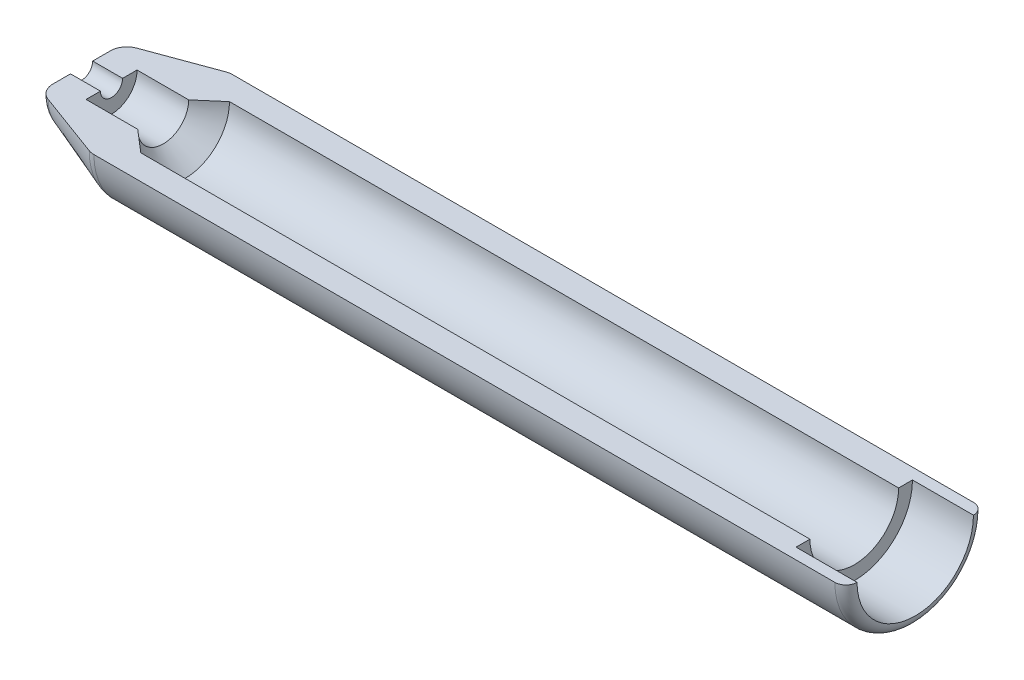
SolidWorks part; units mm, degrees
ref_plane "Front Plane" through (0, 0, 0) normal (0, 0, 1) x (1, 0, 0)
ref_plane "Top Plane" through (0, 0, 0) normal (0, 1, 0) x (1, 0, 0)
ref_plane "Right Plane" through (0, 0, 0) normal (1, 0, 0) x (0, 0, -1)
sketch "Sketch1" plane through (0, 0, 0) normal (0, 1, 0) x (1, 0, 0)
  line L0 (-3.185, 0.1) -> (19.4194, 0.1) construction
  line L1 (-2.4261, 0.9) -> (-1.2536, 1.3315)
  line L2 (12.4176, 1.15) -> (11.3176, 1.15)
  line L3 (11.3176, 1.15) -> (11.3176, 0.9)
  line L4 (2.9176, 0.9) -> (3.6176, 0.9)
  line L7 (-2.0824, 0.3) -> (-2.0824, 0.56)
  line L9 (3.6176, 0.9) -> (11.3176, 0.9)
  line L14 (-2.0824, 0.3) -> (-2.6225, 0.3)
  line L16 (-2.0824, 0.56) -> (-1.15, 0.56)
  line L23 (-1.15, 0.56) -> (-0.7544, 0.9)
  line L24 (12.4176, 5.6171) -> (12.4176, -3.3829) construction
  line L25 (-0.7544, 0.9) -> (2.9176, 0.9)
  line L27 (12.2176, 1.35) -> (-1.15, 1.35)
  line L28 (-2.6225, 0.6185) -> (-2.6225, 0.3)
  arc A0 (-2.4261, 0.9) -> (-2.6225, 0.6185) centre (-2.3225, 0.6185) ccw
  arc A1 (-1.2536, 1.3315) -> (-1.15, 1.35) centre (-1.15, 1.05) cw
  arc A2 (12.2176, 1.35) -> (12.4176, 1.15) centre (12.2176, 1.15) cw
  point P0 (0, 0)
  point P16 (12.4176, 1.35)
  point P24 (12.4176, 1.35)
  dimension "D2" = 0.3
  dimension "D5" = 0.3
  dimension "D6" = 0.46
  dimension "D9" = 0.2
  dimension "D1" = 0.2
  dimension "D3" = 1.25
  dimension "D4" = 0.8
  dimension "D7" = 1.05
  dimension "D8" = 14.5
  dimension "D10" = 1.1
revolve "Revolve1" add sketch "Sketch1" angle 180 about L0 reverse direction yes
